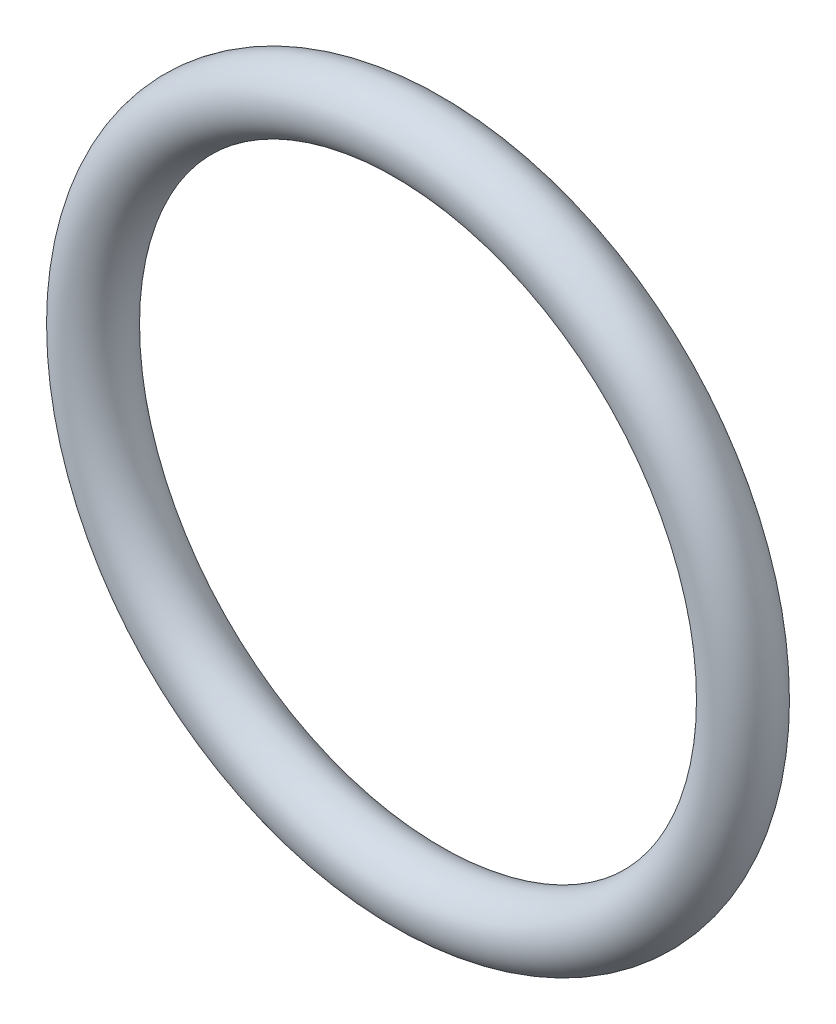
SolidWorks part; units mm, degrees
ref_plane "Front Plane" through (0, 0, 0) normal (0, 0, 1) x (1, 0, 0)
ref_plane "Top Plane" through (0, 0, 0) normal (0, 1, 0) x (1, 0, 0)
ref_plane "Right Plane" through (0, 0, 0) normal (1, 0, 0) x (0, 0, -1)
sketch "Sketch1" plane through (0, 0, 0) normal (0, 0, 1) x (1, 0, 0)
  line L0 (-19.2024, 0) -> (19.2024, 0) construction
  line L1 (-15.6718, 0) -> (15.6718, 0) construction
  line L2 (-13.5781, 13.5781) -> (13.5781, -13.5781) construction
  point P3 (15.6718, 0)
  point P4 (0, 0)
  point P8 (0, 0)
  point P9 (0, 0)
  point P10 (-19.2024, 0)
  point P11 (-15.6718, 0)
  point P14 (0, 0)
  point P15 (13.5781, -13.5781)
  point P16 (19.2024, 0)
  dimension "Actual OD" = 38.4048
  dimension "Actual ID" = 31.3436
  dimension "Actual Width" = 3.5306
  dimension "D1" = 45
sketch "Sketch2" plane through (0, 0, 0) normal (0, 1, 0) x (1, 0, 0)
  line L0 (-19.2024, 0) -> (19.2024, 0) construction
  line L1 (-17.4371, 1.7653) -> (-17.4371, -1.7653) construction
  line L2 (0, -1.7653) -> (0, 1.7653) construction
  circle A0 centre (-17.4371, 0) radius 1.7653
  point P12 (0, 0)
revolve "Revolve1" add sketch "Sketch2" angle 360 about L2
sketch "Sketch3" plane through (0, 0, 0) normal (1, 0, 0) x (0, 0, -1)
  line L0 (-1.7653, 0) -> (1.7653, 0) construction
  line L1 (-1.7653, -11.7538) -> (-1.7653, 11.7538) construction
  point P4 (0, 0)
  point P7 (-1.7653, 0)
  point P9 (-1.7653, -11.7538)
  dimension "D1" = 3.5306
  dimension "D2" = 23.5077
ref_axis "Axis1" through (0, 0, -1.9418) along (0, 0, 1)
equation "\"D1@Sketch3\"=\"Actual Width@Sketch1\""
equation "\"D2@Sketch3\"=\"Actual ID@Sketch1\"*.75"
